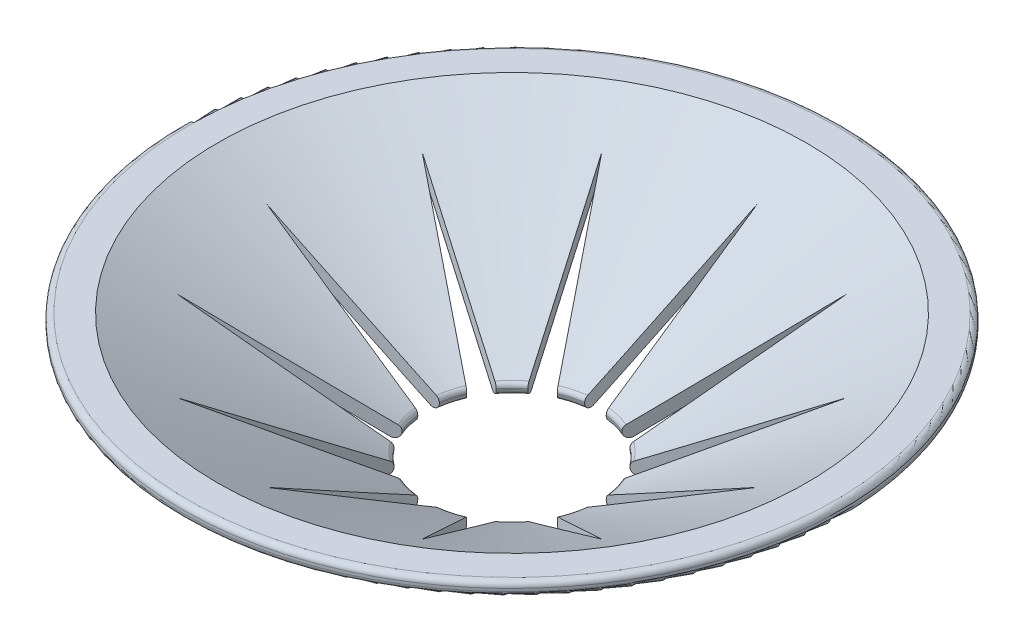
SolidWorks part; units mm, degrees
ref_plane "Plan de face" through (0, 0, 0) normal (0, 0, 1) x (1, 0, 0)
ref_plane "Plan de dessus" through (0, 0, 0) normal (0, 1, 0) x (1, 0, 0)
ref_plane "Plan de droite" through (0, 0, 0) normal (1, 0, 0) x (0, 0, -1)
sketch "Esquisse2" plane through (0, 0, 0) normal (0, 0, 1) x (1, 0, 0)
  line L0 (-29.2564, 0) -> (27.6773, 0) construction
  line L1 (-47, -2) -> (-42, -2)
  line L2 (-47, -2) -> (-47, 0)
  line L3 (-47, 0) -> (-42, 0)
  line L4 (-42, 0) -> (-12, -17.3205)
  line L5 (-12, -17.3205) -> (-12, -19.3205)
  line L6 (0, 0) -> (0, 81.3794) construction
  line L7 (-42, -2) -> (-12, -19.3205)
  dimension "D1" = 12
  dimension "D3" = 47
  dimension "D4" = 5
  dimension "D5" = 2
  dimension "D6" = 5
revolve "Révolution1" add sketch "Esquisse2" angle 360 about L6
fillet "Congé1" radius 0.8 4 edges at (0, -2, -47) (0, 0, -47) (0, -19.3205, -12) (0, -17.3205, -12)
sketch "Esquisse4" plane through (0, 0, 0) normal (0, 1, 0) x (1, 0, 0)
  line L0 (-64.594, 0) -> (-46.7542, 0) construction
  line L1 (-35, 0) -> (-5, 2)
  line L2 (-5, 2) -> (-5, -2)
  line L3 (-5, -2) -> (-35, 0)
  line L4 (-30.3109, 17.5) -> (-3.3301, 4.2321)
  line L5 (-5.3301, 0.7679) -> (-30.3109, 17.5)
  line L6 (-3.3301, 4.2321) -> (-5.3301, 0.7679)
  line L7 (-17.5, 30.3109) -> (-0.7679, 5.3301)
  line L8 (-4.2321, 3.3301) -> (-17.5, 30.3109)
  line L9 (-0.7679, 5.3301) -> (-4.2321, 3.3301)
  line L10 (0, 35) -> (2, 5)
  line L11 (-2, 5) -> (0, 35)
  line L12 (2, 5) -> (-2, 5)
  line L13 (17.5, 30.3109) -> (4.2321, 3.3301)
  line L14 (0.7679, 5.3301) -> (17.5, 30.3109)
  line L15 (4.2321, 3.3301) -> (0.7679, 5.3301)
  line L16 (30.3109, 17.5) -> (5.3301, 0.7679)
  line L17 (3.3301, 4.2321) -> (30.3109, 17.5)
  line L18 (5.3301, 0.7679) -> (3.3301, 4.2321)
  line L19 (35, 0) -> (5, -2)
  line L20 (5, 2) -> (35, 0)
  line L21 (5, -2) -> (5, 2)
  line L22 (30.3109, -17.5) -> (3.3301, -4.2321)
  line L23 (5.3301, -0.7679) -> (30.3109, -17.5)
  line L24 (3.3301, -4.2321) -> (5.3301, -0.7679)
  line L25 (17.5, -30.3109) -> (0.7679, -5.3301)
  line L26 (4.2321, -3.3301) -> (17.5, -30.3109)
  line L27 (0.7679, -5.3301) -> (4.2321, -3.3301)
  line L28 (0, -35) -> (-2, -5)
  line L29 (2, -5) -> (0, -35)
  line L30 (-2, -5) -> (2, -5)
  line L31 (-17.5, -30.3109) -> (-4.2321, -3.3301)
  line L32 (-0.7679, -5.3301) -> (-17.5, -30.3109)
  line L33 (-4.2321, -3.3301) -> (-0.7679, -5.3301)
  line L34 (-30.3109, -17.5) -> (-5.3301, -0.7679)
  line L35 (-3.3301, -4.2321) -> (-30.3109, -17.5)
  line L36 (-5.3301, -0.7679) -> (-3.3301, -4.2321)
  circle A0 centre (0, 0) radius 42 construction
  point P44 (0, 0)
  dimension "D3" = 35
  dimension "D1" = 2
  dimension "D2" = 2
  dimension "D4" = 5
  dimension "D5" = 12
extrude "Enlèv. mat.-Extru.1" cut sketch "Esquisse4" against normal blind 30 contours L27 L30 L29 L25 L26 L22 L24 | L35 L34 L36 | L32 L31 L33 | L29 L28 L30 | L22 L24 L23 | L19 L21 L20 | L16 L18 L17 | L14 L13 L15 | L11 L10 L12 | L7 L9 L8 | L4 L6 L5 | L1 L2 L3 region at (7.7108, 0, 13.3555)
